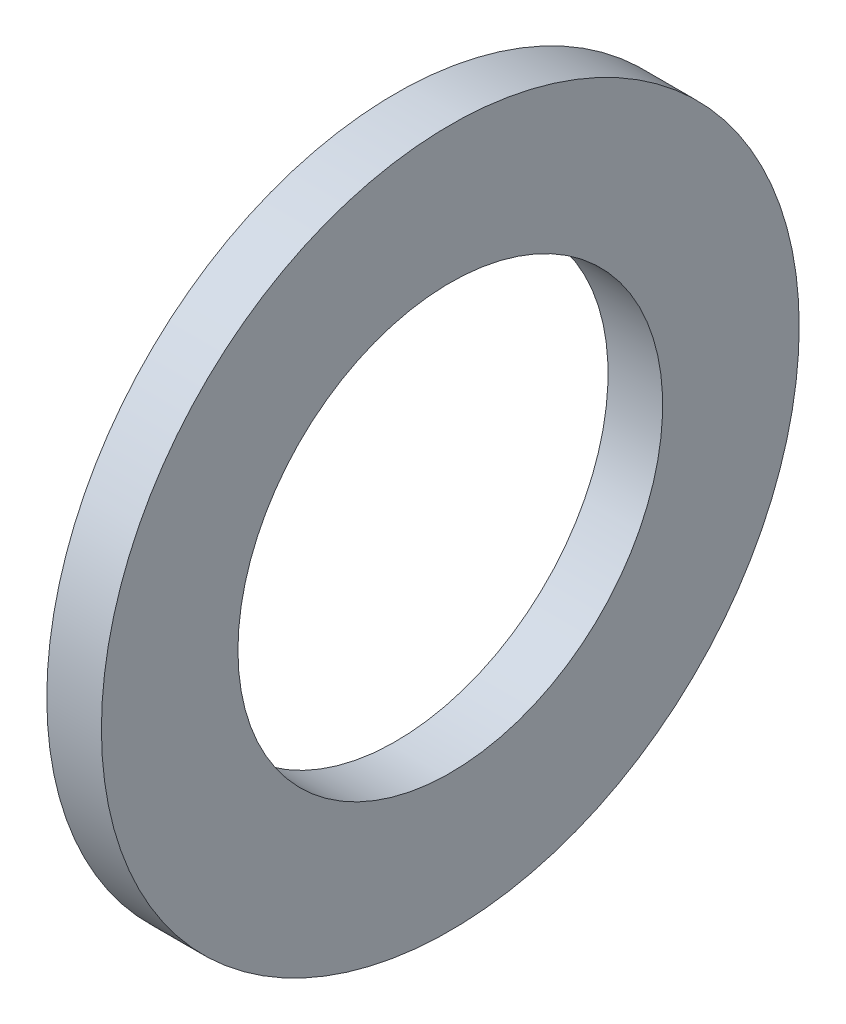
SolidWorks part; units mm, degrees
ref_plane "Plane1" through (0, 0, 0) normal (0, 0, 1) x (1, 0, 0)
ref_plane "Plane2" through (0, 0, 0) normal (0, 1, 0) x (1, 0, 0)
ref_plane "Plane3" through (0, 0, 0) normal (1, 0, 0) x (0, 0, -1)
sketch "Sketch1" plane through (0, 0, 0) normal (0, 0, 1) x (1, 0, 0)
  line L0 (-34.925, 0) -> (9.525, 0) construction
  line L1 (0, 35) -> (0, 57.5)
  line L2 (0, 57.5) -> (-9, 57.5)
  line L3 (-9, 57.5) -> (-9, 35)
  line L4 (-9, 35) -> (0, 35)
  dimension "Thickness" = 9
  dimension "Inside_dia" = 70
  dimension "Outside_dia" = 115
revolve "Base-Revolve" add sketch "Sketch1" angle 360 about L0
